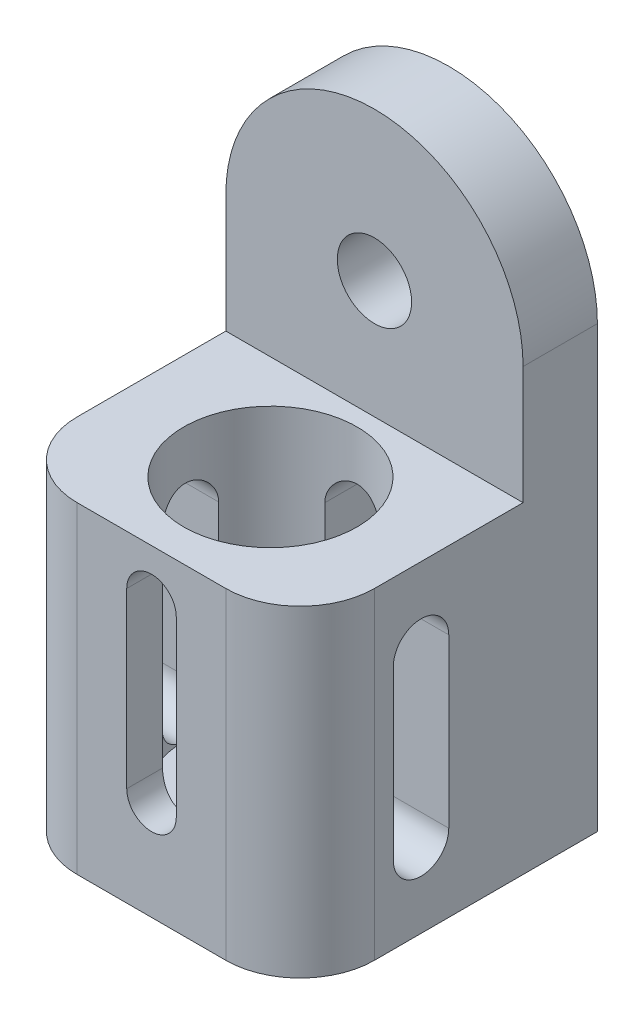
SolidWorks part; units mm, degrees
material "6061-T6 (SS)"
ref_plane "Front Plane" through (0, 0, 0) normal (0, 0, 1) x (1, 0, 0)
ref_plane "Top Plane" through (0, 0, 0) normal (0, 1, 0) x (1, 0, 0)
ref_plane "Right Plane" through (0, 0, 0) normal (1, 0, 0) x (0, 0, -1)
ref_axis "X-axis" through (-88.99, 0, 0) along (1, 0, 0)
ref_axis "Y-axis" through (0, 55, 0) along (0, -1, 0)
ref_axis "Z-axis" through (0, 0, -88.99) along (0, 0, 1)
sketch "Sketch1" plane through (0, 0, 0) normal (1, 0, 0) x (0, 0, -1)
  line L0 (0, 0) -> (-76.2, 0)
  line L1 (-76.2, 0) -> (-76.2, 82.55)
  line L2 (-76.2, 82.55) -> (-19.05, 82.55)
  line L3 (-19.05, 82.55) -> (-19.05, 112.776)
  line L4 (-19.05, 112.776) -> (0, 112.776)
  line L5 (0, 112.776) -> (0, 0)
  dimension "D1" = 82.55
  dimension "D2" = 112.776
  dimension "D3" = 76.2
  dimension "D4" = 19.05
extrude "Boss-Extrude1" add sketch "Sketch1" against normal mid plane 76.2
sketch "Sketch2" plane through (0, 0, 0) normal (0, 0, 1) x (1, 0, 0)
  line L1 (-38.1, 112.776) -> (38.1, 112.776)
  arc A1 (-38.1, 112.776) -> (38.1, 112.776) centre (0, 112.776) cw
extrude "Boss-Extrude2" add sketch "Sketch2" along normal blind 19.05
sketch "Sketch3" plane through (38.1, 0, 0) normal (1, 0, 0) x (0, 0, -1)
  line L0 (-45.212, 62.738) -> (-45.212, 19.812) construction
  line L1 (-38.1, 62.738) -> (-38.1, 19.812)
  line L2 (-52.324, 62.738) -> (-52.324, 19.812)
  line L3 (-76.2, 0) -> (0, 0) construction
  line L4 (-76.2, 82.55) -> (-76.2, 0) construction
  arc A0 (-38.1, 62.738) -> (-52.324, 62.738) centre (-45.212, 62.738) ccw
  arc A1 (-52.324, 19.812) -> (-38.1, 19.812) centre (-45.212, 19.812) ccw
  point P2 (-45.212, 41.275)
  dimension "D1" = 14.224
  dimension "D2" = 19.812
  dimension "D3" = 42.926
  dimension "D4" = 30.988
extrude "Cut-Extrude1" cut sketch "Sketch3" against normal through all
hole_wizard "1/4 (1.75) Diameter Hole1" positions "Sketch4" profile "Sketch5" hole size "1/4" standard "ANSI Inch"
sketch "Sketch4" plane through (0, 82.55, 0) normal (0, 1, 0) x (1, 0, 0)
  line L0 (-38.1, -76.2) -> (38.1, -76.2) construction
  point P0 (0, -45.72)
  dimension "D1" = 30.48
sketch "Sketch5" plane through (0, 82.55, 45.72) normal (1, 0, 0) x (0, 0, 1)
  line L0 (0, 0) -> (0, 69.85)
  line L1 (0, 69.85) -> (22.225, 69.85)
  line L2 (22.225, 69.85) -> (22.225, 0)
  line L5 (22.225, 0) -> (0, 0)
  line L10 (0, 69.85) -> (-22.225, 69.85) construction
  line L11 (0, -6.35) -> (0, 107.95) construction
  dimension "Hole Dia." = 44.45
  dimension "Hole Depth" = 69.85
  dimension "Drill Angle" = 180
fillet "Fillet1" radius 19.05 2 edges at (-38.1, 41.275, 76.2) (38.1, 41.275, 76.2)
sketch "Sketch6" plane through (0, 0, 76.2) normal (0, 0, 1) x (1, 0, 0)
  line L0 (0, 25.4) -> (0, 69.85) construction
  line L1 (-6.35, 25.4) -> (-6.35, 69.85)
  line L2 (6.35, 25.4) -> (6.35, 69.85)
  line L3 (-19.05, 0) -> (19.05, 0) construction
  arc A0 (-6.35, 25.4) -> (6.35, 25.4) centre (0, 25.4) ccw
  arc A1 (6.35, 69.85) -> (-6.35, 69.85) centre (0, 69.85) ccw
  point P2 (0, 47.625)
  dimension "D1" = 44.45
  dimension "D2" = 12.7
  dimension "D3" = 25.4
extrude "Cut-Extrude2" cut sketch "Sketch6" against normal blind 19.05
sketch "Sketch7" plane through (0, 0, 0) normal (0, 0, -1) x (-1, 0, 0)
  line L0 (0, 19.812) -> (0, 62.738) construction
  line L1 (-7.112, 19.812) -> (-7.112, 62.738)
  line L2 (7.112, 19.812) -> (7.112, 62.738)
  line L3 (38.1, 0) -> (-38.1, 0) construction
  arc A0 (-7.112, 19.812) -> (7.112, 19.812) centre (0, 19.812) ccw
  arc A1 (7.112, 62.738) -> (-7.112, 62.738) centre (0, 62.738) ccw
  point P2 (0, 41.275)
  point P8 (0, 0)
  dimension "D1" = 42.926
  dimension "D2" = 19.812
  dimension "D3" = 14.224
extrude "Cut-Extrude3" cut sketch "Sketch7" against normal blind 25.4
hole_wizard "1/4 (0.75) Diameter Hole1" positions "Sketch8" profile "Sketch9" hole size "1/4" standard "ANSI Inch" end condition through all
sketch "Sketch8" plane through (0, 0, 19.05) normal (0, 0, 1) x (1, 0, 0)
  point P0 (0, 112.776)
sketch "Sketch9" plane through (0, 112.776, 19.05) normal (1, 0, 0) x (0, -1, 0)
  line L0 (0, 0) -> (0, 19.05)
  line L1 (0, 19.05) -> (9.525, 19.05)
  line L2 (9.525, 19.05) -> (9.525, 0)
  line L5 (9.525, 0) -> (0, 0)
  line L11 (0, -6.35) -> (0, 107.95) construction
  dimension "Thru Hole Dia." = 19.05
  dimension "Thru Hole Depth" = 19.05
